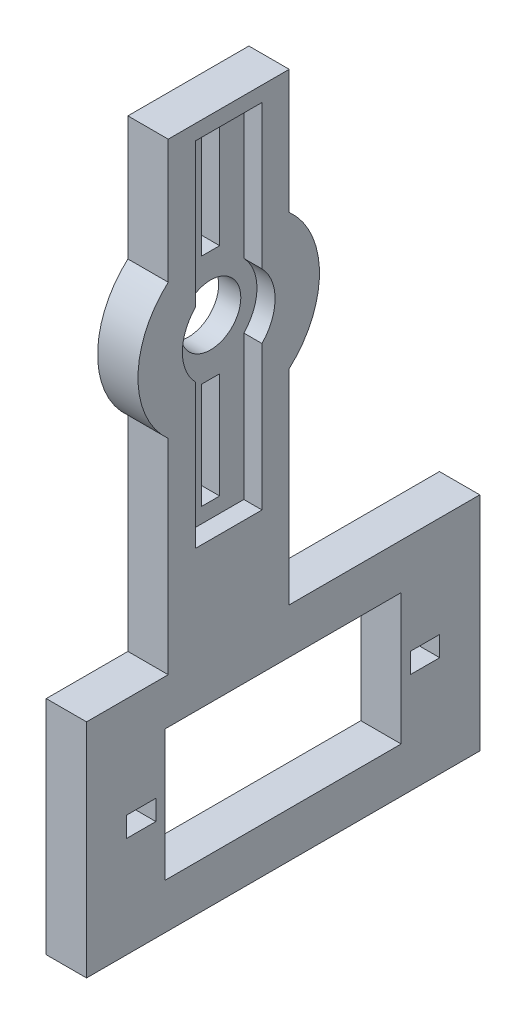
SolidWorks part; units mm, degrees
ref_plane "Front Plane" through (0, 0, 0) normal (0, 0, 1) x (1, 0, 0)
ref_plane "Top Plane" through (0, 0, 0) normal (0, 1, 0) x (1, 0, 0)
ref_plane "Right Plane" through (0, 0, 0) normal (1, 0, 0) x (0, 0, -1)
sketch "Sketch1" plane through (0, 0, 0) normal (1, 0, 0) x (0, 0, -1)
  circle A0 centre (52, 18) radius 9
extrude "Boss-Extrude1" add sketch "Sketch1" along normal blind 4 from offset 59.6 offset against normal yes
sketch "Sketch2" plane through (0, 0, 0) normal (0, 0, 1) x (1, 0, 0)
  line L1 (-59.6, -12) -> (-55.6, -12)
  line L2 (-59.6, -12) -> (-59.6, 37)
  line L3 (-59.6, 37) -> (-55.6, 37)
  line L4 (-55.6, -12) -> (-55.6, 37)
extrude "Boss-Extrude2" add sketch "Sketch2" along normal blind 12 from offset 58 offset against normal yes
sketch "Sketch3" plane through (0, 0, 0) normal (0, 0, 1) x (1, 0, 0)
  line L1 (-59.6, -31) -> (-55.6, -31)
  line L2 (-59.6, -31) -> (-59.6, -9)
  line L3 (-59.6, -9) -> (-55.6, -9)
  line L4 (-55.6, -31) -> (-55.6, -9)
extrude "Boss-Extrude3" add sketch "Sketch3" along normal blind 39 from offset 76.9 offset against normal yes
sketch "Sketch4" plane through (0, 0, 0) normal (1, 0, 0) x (0, 0, -1)
  circle A0 centre (52, 18) radius 4.6
extrude "Boss-Extrude4" add sketch "Sketch4" along normal blind 2.3 from offset 57.4 separate body offset against normal yes
combine bodies "Combine1" operation type subtract main body 103 bodies to subtract 104
sketch "Sketch5" plane through (0, 0, 0) normal (0, 0, 1) x (1, 0, 0)
  line L1 (-57.4, 18) -> (-55.1, 18)
  line L2 (-57.4, 18) -> (-57.4, 35.5)
  line L3 (-57.4, 35.5) -> (-55.1, 35.5)
  line L4 (-55.1, 18) -> (-55.1, 35.5)
extrude "Boss-Extrude5" add sketch "Sketch5" along normal blind 6.6 from offset 55.3 separate body offset against normal yes
combine bodies "Combine2" operation type subtract main body 105 bodies to subtract 106
sketch "Sketch6" plane through (0, 0, 0) normal (0, 0, 1) x (1, 0, 0)
  line L1 (-60.6, 23.5) -> (-54.6, 23.5)
  line L2 (-60.6, 23.5) -> (-60.6, 34)
  line L3 (-60.6, 34) -> (-54.6, 34)
  line L4 (-54.6, 23.5) -> (-54.6, 34)
extrude "Boss-Extrude6" add sketch "Sketch6" along normal blind 1.8 from offset 52.9 separate body offset against normal yes
combine bodies "Combine3" operation type subtract main body 107 bodies to subtract 108
sketch "Sketch7" plane through (0, 0, 0) normal (0, 0, 1) x (1, 0, 0)
  line L1 (-57.4, 0.5) -> (-55.1, 0.5)
  line L2 (-57.4, 0.5) -> (-57.4, 18)
  line L3 (-57.4, 18) -> (-55.1, 18)
  line L4 (-55.1, 0.5) -> (-55.1, 18)
extrude "Boss-Extrude7" add sketch "Sketch7" along normal blind 6.6 from offset 55.3 separate body offset against normal yes
combine bodies "Combine4" operation type subtract main body 109 bodies to subtract 110
sketch "Sketch8" plane through (0, 0, 0) normal (0, 0, 1) x (1, 0, 0)
  line L1 (-60.6, 2) -> (-54.6, 2)
  line L2 (-60.6, 2) -> (-60.6, 12.5)
  line L3 (-60.6, 12.5) -> (-54.6, 12.5)
  line L4 (-54.6, 2) -> (-54.6, 12.5)
extrude "Boss-Extrude8" add sketch "Sketch8" along normal blind 1.8 from offset 52.9 separate body offset against normal yes
combine bodies "Combine5" operation type subtract main body 111 bodies to subtract 112
sketch "Sketch9" plane through (0, 0, 0) normal (1, 0, 0) x (0, 0, -1)
  circle A0 centre (52, 18) radius 3
extrude "Boss-Extrude9" add sketch "Sketch9" along normal blind 6 from offset 60.6 separate body offset against normal yes
combine bodies "Combine6" operation type subtract main body 113 bodies to subtract 114
sketch "Sketch10" plane through (0, 0, 0) normal (0, 0, 1) x (1, 0, 0)
  line L1 (-60.6, -26.5) -> (-54.6, -26.5)
  line L2 (-60.6, -26.5) -> (-60.6, -13.5)
  line L3 (-60.6, -13.5) -> (-54.6, -13.5)
  line L4 (-54.6, -26.5) -> (-54.6, -13.5)
extrude "Boss-Extrude10" add sketch "Sketch10" along normal blind 23.4 from offset 69.1 separate body offset against normal yes
combine bodies "Combine7" operation type subtract main body 115 bodies to subtract 116
sketch "Sketch11" plane through (0, 0, 0) normal (0, 0, 1) x (1, 0, 0)
  line L1 (-60.6, -21) -> (-54.6, -21)
  line L2 (-60.6, -21) -> (-60.6, -19)
  line L3 (-60.6, -19) -> (-54.6, -19)
  line L4 (-54.6, -21) -> (-54.6, -19)
extrude "Boss-Extrude11" add sketch "Sketch11" along normal blind 2.9 from offset 72.925 separate body offset against normal yes
combine bodies "Combine8" operation type subtract main body 117 bodies to subtract 118
sketch "Sketch12" plane through (0, 0, 0) normal (0, 0, 1) x (1, 0, 0)
  line L1 (-60.6, -21) -> (-54.6, -21)
  line L2 (-60.6, -21) -> (-60.6, -19)
  line L3 (-60.6, -19) -> (-54.6, -19)
  line L4 (-54.6, -21) -> (-54.6, -19)
extrude "Boss-Extrude12" add sketch "Sketch12" along normal blind 2.9 from offset 44.775 separate body offset against normal yes
combine bodies "Combine9" operation type subtract main body 119 bodies to subtract 120
